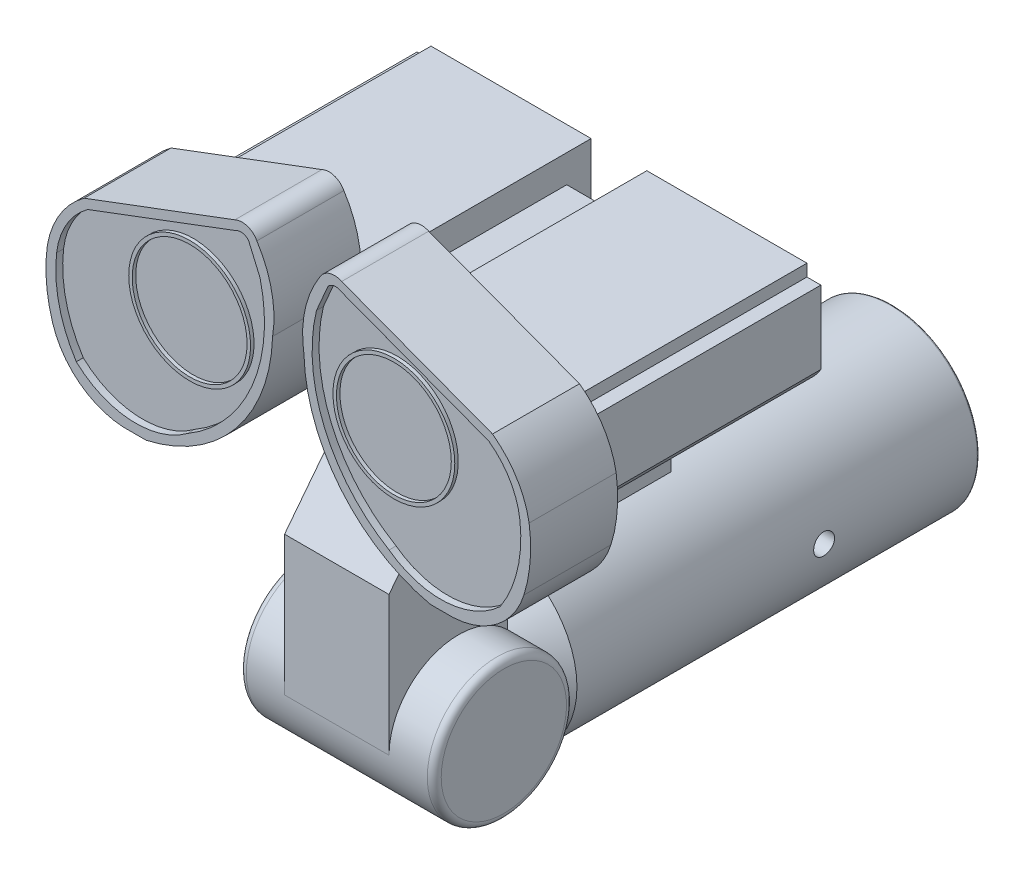
SolidWorks part; units mm, degrees
material "Polyethylene Cross-Linked"
ref_plane "Front" through (0, 0, 0) normal (0, 0, 1) x (1, 0, 0)
ref_plane "Top" through (0, 0, 0) normal (0, 1, 0) x (1, 0, 0)
ref_plane "Right" through (0, 0, 0) normal (1, 0, 0) x (0, 0, -1)
sketch "Sketch2" plane through (0, 0, 0) normal (1, 0, 0) x (0, 0, -1)
  line L0 (0, 1.25) -> (-5.75, 1.25)
  line L3 (3.3, 0) -> (-3.3, 0) construction
  line L4 (-5.75, 1.25) -> (-6.25, 0.75)
  line L5 (-6.25, 0.75) -> (-6.25, 0)
  line L7 (0, 0) -> (0, 1.25)
  line L8 (-6.25, 0) -> (0.1636, 0)
  ellipse E0 centre (0, 0) end of major axis (0, 1.25) minor radius 0.1636 (0.1636, 0) -> (0, 1.25) ccw
  dimension "D1" = 5.75
  dimension "D2" = 1.25
  dimension "D3" = 0.75
  dimension "D4" = 0.5
revolve "Bottom tube" add sketch "Sketch2" angle 360 about L8 region at (0, 0.6175, 3.0769) region at (0, 0.5305, -0.0694)
sketch "Sketch3" plane through (0, 0, 0) normal (1, 0, 0) x (0, 0, -1)
  line L0 (1.375, 0) -> (-1.375, 0) construction
  line L1 (-6.25, 0.75) -> (-6.25, -0.75) construction
  circle A1 centre (-6.95, 0) radius 1
  dimension "D1" = 2
  dimension "D2" = 0.7
extrude "Hinge connected to bottom tube" add sketch "Sketch3" along normal blind 1.4 and the other way blind 1.4
fillet "fillet on hinge" radius 0.1 2 edges at (1.4, 0, 7.95) (-1.4, 0, 7.95)
sketch "Sketch4" plane through (0, 0, 0) normal (1, 0, 0) x (0, 0, -1)
  line L0 (-7.95, 0) -> (-7.95, 2)
  line L1 (-5.75, 1.25) -> (-5.75, -1.25) construction
  line L2 (1.54, 0) -> (-1.54, 0) construction
  line L3 (-6.25, 0.7141) -> (-6.25, 1.5)
  line L4 (-3.8968, 4) -> (-6.3968, 4)
  line L5 (-6.25, 1.5) -> (-3.8968, 1.5)
  line L6 (-3.8968, 1.5) -> (-3.8968, 4)
  line L7 (-6.3968, 4) -> (-7.95, 2)
  line L9 (0, 1.25) -> (-5.75, 1.25) construction
  arc A0 (-6.25, 0.7141) -> (-7.95, 0) centre (-6.95, 0) ccw
  circle A1 centre (-6.95, 0) radius 1 construction
  arc A2 (-6.25, -0.7141) -> (-6.25, 0.7141) centre (-6.95, 0) ccw construction
  dimension "D1" = 0.25
  dimension "D2" = 2
  dimension "D3" = 0.5
  dimension "D4" = 2.5
  dimension "D5" = 2.5
extrude "base connected to eyes" add sketch "Sketch4" along normal blind 0.75 and the other way blind 0.75 contours A0 L0 L7 L4 L6 L5 L3
sketch "Sketch5" plane through (0, 0, 3.8968) normal (0, 0, -1) x (-1, 0, 0)
  line L2 (0, 2.8875) -> (0, -2.8875) construction
  line L7 (2.25, 3.5) -> (-2.25, 3.5)
  line L9 (0.75, 4) -> (-0.75, 4) construction
  line L10 (-2.7, 5.07) -> (-2.7, 4.8972)
  line L11 (-2.7, 4.8972) -> (-2.9, 4.8972)
  line L12 (-2.7, 4.8972) -> (-2.9, 4.8972)
  line L13 (-2.7, 5.07) -> (2.7, 5.07)
  line L14 (2.9, 4.8972) -> (2.9, 3.8472)
  line L15 (-2.9, 4.8972) -> (-2.9, 3.8472)
  line L17 (2.7, 4.8972) -> (2.9, 4.8972)
  line L18 (2.7, 5.07) -> (2.7, 4.8972)
  arc A2 (-2.9, 3.8472) -> (-2.25, 3.5) centre (-2.2926, 4.2023) ccw
  arc A3 (2.9, 3.8472) -> (2.25, 3.5) centre (2.2926, 4.2023) cw
  line M5 (0.75, 4) -> (-0.75, 4)
  line M6 (-0.75, 4) -> (-0.75, 1.5)
  line M8 (0.75, 1.5) -> (0.75, 4)
  dimension "D3" = 0.5
  dimension "D5" = 1.07
  dimension "D7" = 0.2
  dimension "D4" = 5.4
  dimension "D10" = 1.05
  dimension "D11" = 0.2
extrude "Eye backing" add sketch "Sketch5" against normal blind 3.5 contours A3 L14 L17 L18 L13 L10 L11 L15 A2 L7 M6 M5 M8 region at (0, 4.3385, 3.8968)
sketch "Sketch7" plane through (0, 5.07, 0) normal (0, 1, 0) x (1, 0, 0)
  line L0 (2.7, -3.8968) -> (-2.7, -3.8968) construction
  line L1 (-0.4, -3.8968) -> (0.4, -3.8968)
  line L2 (-0.4, -3.8968) -> (-0.4, -7.3968)
  line L3 (-0.4, -7.3968) -> (0.4, -7.3968)
  line L4 (0.4, -3.8968) -> (0.4, -7.3968)
  line L5 (2.7, -7.3968) -> (-2.7, -7.3968) construction
  line L6 (0, -2.8875) -> (0, 2.8875) construction
  dimension "D1" = 0.4
  dimension "D2" = 0.4
extrude "Eye backing details" cut sketch "Sketch7" against normal blind 1.07
sketch "Sketch8" plane through (0, 4, 0) normal (0, 1, 0) x (1, 0, 0)
  line L0 (-0.4, -3.8968) -> (-0.4, -7.3968) construction
  line L1 (-0.4, -4.2468) -> (0.4, -4.2468)
  line L2 (-0.4, -4.2468) -> (-0.4, -6.1468)
  line L3 (-0.4, -6.1468) -> (0.4, -6.1468)
  line L4 (0.4, -4.2468) -> (0.4, -6.1468)
  line L5 (0.4, -7.3968) -> (0.4, -3.8968) construction
  line L7 (0.4, -6.3968) -> (-0.4, -6.3968) construction
  line L8 (0.4, -3.8968) -> (-0.4, -3.8968) construction
  dimension "D1" = 0.25
  dimension "D2" = 0.35
extrude "Middle of eye backing" add sketch "Sketch8" along normal blind 0.67
sketch "Eye sketch" plane through (0, 0, 3.8968) normal (0, 0, -1) x (-1, 0, 0)
  line L0 (0, 4.8457) -> (0, -4.8457) construction
  line L1 (2.3717, 2.871) -> (2.0415, 2.871)
  line L2 (0.7671, 6.2506) -> (2.9333, 5.4363)
  line L10 (50.3928, 177.5032) -> (290.3928, 177.5032) construction
  line L11 (-0.7671, 6.2506) -> (-2.9333, 5.4363)
  line L12 (-2.3717, 2.871) -> (-2.0415, 2.871)
  arc A0 (-2.9333, 5.4363) -> (-3.4597, 4.5924) centre (-2.1493, 4.3611) ccw
  arc A1 (-3.4597, 4.5924) -> (-3.3844, 3.658) centre (-1.3693, 4.2908) ccw
  arc A2 (-3.3844, 3.658) -> (-2.3717, 2.871) centre (-2.296, 4.0134) ccw
  arc A3 (-2.0415, 2.871) -> (-0.2253, 5.07) centre (-2.5477, 5.1386) ccw
  arc A4 (-0.2253, 5.07) -> (-0.451, 6.1456) centre (-1.7381, 5.3141) ccw
  arc A5 (-0.7671, 6.2506) -> (-0.451, 6.1456) centre (-0.6636, 6.0339) cw
  circle A6 centre (-1.4666, 4.7464) radius 0.95
  circle A7 centre (-1.4666, 4.7464) radius 0.375
  arc A8 (0.7671, 6.2506) -> (0.451, 6.1456) centre (0.6636, 6.0339) ccw
  arc A9 (0.2253, 5.07) -> (0.451, 6.1456) centre (1.7381, 5.3141) cw
  arc A10 (2.0415, 2.871) -> (0.2253, 5.07) centre (2.5477, 5.1386) cw
  circle A11 centre (1.4666, 4.7464) radius 0.375
  circle A12 centre (1.4666, 4.7464) radius 0.95
  arc A13 (3.3844, 3.658) -> (2.3717, 2.871) centre (2.296, 4.0134) cw
  arc A14 (3.4597, 4.5924) -> (3.3844, 3.658) centre (1.3693, 4.2908) cw
  arc A15 (2.9333, 5.4363) -> (3.4597, 4.5924) centre (2.1493, 4.3611) cw
  dimension "D1" = 1.9
  dimension "D2" = 0.75
  dimension "D6" = 1.3307
sketch "Sketch12" plane through (0, 0, 7.3968) normal (0, 0, 1) x (1, 0, 0)
  line L0 (-0.7671, 6.2506) -> (-2.9333, 5.4363)
  line L1 (-2.3717, 2.871) -> (-2.0415, 2.871)
  line L2 (0, -3.476) -> (0, 3.476) construction
  line L3 (2.3717, 2.871) -> (2.0415, 2.871)
  line L4 (0.7671, 6.2506) -> (2.9333, 5.4363)
  arc A0 (-2.9333, 5.4363) -> (-3.4597, 4.5924) centre (-2.1493, 4.3611) ccw
  arc A1 (-3.4597, 4.5924) -> (-3.3844, 3.658) centre (-1.3693, 4.2908) ccw
  arc A2 (-3.3844, 3.658) -> (-2.3717, 2.871) centre (-2.31, 3.9954) ccw
  arc A3 (-2.0415, 2.871) -> (-0.2253, 5.07) centre (-2.5477, 5.1386) ccw
  arc A4 (-0.2253, 5.07) -> (-0.451, 6.1456) centre (-1.7381, 5.3141) ccw
  arc A5 (-0.451, 6.1456) -> (-0.7671, 6.2506) centre (-0.6636, 6.0339) ccw
  circle A7 centre (-1.4666, 4.7464) radius 0.875
  arc A8 (2.0415, 2.871) -> (0.2253, 5.07) centre (2.5477, 5.1386) cw
  arc A9 (3.3844, 3.658) -> (2.3717, 2.871) centre (2.31, 3.9954) cw
  arc A11 (0.451, 6.1456) -> (0.7671, 6.2506) centre (0.6636, 6.0339) cw
  arc A12 (0.2253, 5.07) -> (0.451, 6.1456) centre (1.7381, 5.3141) cw
  arc A13 (3.4597, 4.5924) -> (3.3844, 3.658) centre (1.3693, 4.2908) cw
  arc A14 (2.9333, 5.4363) -> (3.4597, 4.5924) centre (2.1493, 4.3611) cw
  circle A15 centre (1.4666, 4.7464) radius 0.875
  circle A16 centre (-1.4666, 4.7464) radius 0.825
  circle A17 centre (1.4666, 4.7464) radius 0.825
  line M1 (-0.75, 4) -> (-0.4, 4)
  line M2 (-0.4, 4) -> (-0.4, 5.07)
  line M3 (-0.4, 5.07) -> (-2.7, 5.07)
  line M4 (-2.7, 5.07) -> (-2.7, 4.8972)
  line M5 (-2.7, 4.8972) -> (-2.9, 4.8972)
  line M6 (-2.9, 4.8972) -> (-2.9, 3.8472)
  arc M7 (-2.9, 3.8472) -> (-2.25, 3.5) centre (-2.2926, 4.2023) ccw
  line M8 (-2.25, 3.5) -> (-0.75, 3.5)
  line M9 (-0.75, 3.5) -> (-0.75, 4)
  dimension "D1" = 1.75
  dimension "D3" = 0.05
extrude "Outer eye" add sketch "Sketch12" along normal blind 1.25 contours A7 A3 A4 A5 L0 A0 A1 A2 L1 M3 M2 M8 M7 M6 M5 M4 | A3 M9 M1 | A7 A3 M3 M4 M5 M6 M7 M8 M9 M1 M2 | A14 L4 A11 A12 A8 L3 A9 A13 A15 region at (-0.6028, 6.217, 7.3968) region at (-0.484, 4.1372, 7.3968) region at (-0.6717, 3.8855, 7.3968) region at (2.2066, 2.9183, 7.3968)
sketch "Sketch13" plane through (0, 0, 8.6468) normal (0, 0, 1) x (1, 0, 0)
  line L0 (-0.758, 6.1213) -> (-2.8802, 5.3222)
  line L1 (-0.5701, 6.0916) -> (-0.4049, 5.7086)
  line L2 (0, -3.476) -> (0, 3.476) construction
  line L3 (0.5701, 6.0916) -> (0.4049, 5.7086)
  line L4 (0.758, 6.1213) -> (2.8802, 5.3222)
  arc A0 (-2.8802, 5.3222) -> (-3.3276, 4.5598) centre (-2.2369, 4.4322) ccw
  arc A1 (-3.3276, 4.5598) -> (-3.0448, 3.3456) centre (-1.4983, 4.3458) ccw
  arc A2 (-3.0448, 3.3456) -> (-1.4485, 3.2519) centre (-2.1905, 4.2551) ccw
  arc A3 (-1.4485, 3.2519) -> (-0.4049, 5.7086) centre (-2.5792, 5.1822) ccw
  arc A5 (-0.758, 6.1213) -> (-0.5701, 6.0916) centre (-0.6809, 5.9995) cw
  arc A6 (1.4485, 3.2519) -> (0.4049, 5.7086) centre (2.5792, 5.1822) cw
  arc A7 (0.758, 6.1213) -> (0.5701, 6.0916) centre (0.6809, 5.9995) ccw
  arc A8 (3.0448, 3.3456) -> (1.4485, 3.2519) centre (2.1905, 4.2551) cw
  arc A9 (3.3276, 4.5598) -> (3.0448, 3.3456) centre (1.4983, 4.3458) cw
  arc A10 (2.8802, 5.3222) -> (3.3276, 4.5598) centre (2.2369, 4.4322) cw
extrude "Inner eye cut" cut sketch "Sketch13" against normal blind 0.1
extrude "Outer lens" add sketch "Sketch12<5>" along normal blind 1.2 contours A16 A7 M3 | A16 A7 M3 | A15 A17 region at (-1.6274, 3.9079, 7.3968) region at (-0.6807, 5.0872, 7.3968) region at (0.6164, 4.7464, 7.3968)
sketch "Sketch12<5>" plane through (0, 0, 7.3968) normal (0, 0, 1) x (1, 0, 0) same geometry as "Sketch12"
extrude "Inner lens cut" add sketch "Sketch12<7>" along normal blind 1.15 contours A16 M3 | A16 M3 | A17 region at (-1.4666, 5.2769, 7.3968) region at (-1.4666, 4.563, 7.3968) region at (1.4666, 4.7464, 7.3968)
sketch "Sketch12<7>" plane through (0, 0, 7.3968) normal (0, 0, 1) x (1, 0, 0) same geometry as "Sketch12"
sketch "Sketch15" plane through (0, 0, 0) normal (1, 0, 0) x (0, 0, -1)
  line L0 (3.8295, 0) -> (-3.8295, 0) construction
  line L1 (0, 3.8295) -> (0, -3.8295) construction
  circle A0 centre (-2.2, 0) radius 0.15
  dimension "D1" = 0.3
  dimension "D2" = 2.2
extrude "Cut-Extrude3" cut sketch "Sketch15" against normal up to next and the other way up to next
extrude "Boss-Extrude16" add sketch "Sketch12<6>" along normal blind 1.15 contours A16 M3 | A16 M3 | A17 region at (-1.4666, 5.2769, 7.3968) region at (-1.4666, 4.563, 7.3968) region at (1.4666, 4.7464, 7.3968)
sketch "Sketch12<6>" plane through (0, 0, 7.3968) normal (0, 0, 1) x (1, 0, 0) same geometry as "Sketch12"
scale "Scale1" bodies to scale 119 scale about origin uniform scaling yes scale factor 1.75
equation "\"D2@Sketch7\"=\"D1@Sketch7\""
